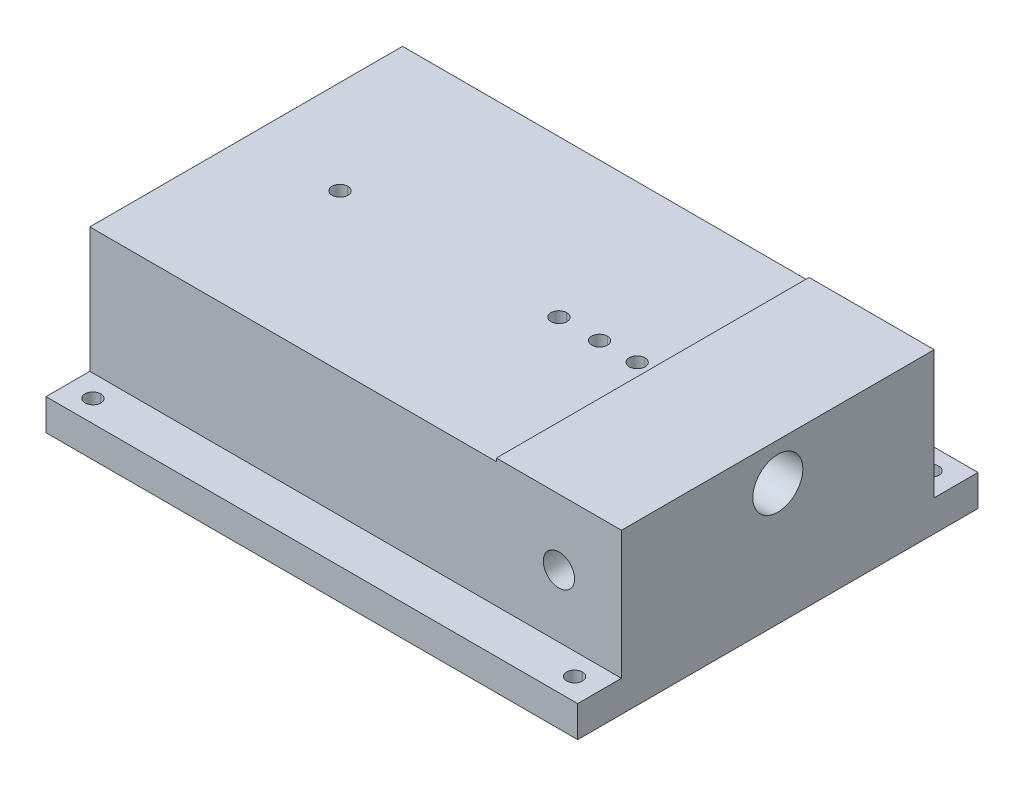
SolidWorks part; units mm, degrees
ref_plane "Front Plane" through (0, 0, 0) normal (0, 0, 1) x (1, 0, 0)
ref_plane "Top Plane" through (0, 0, 0) normal (0, 1, 0) x (1, 0, 0)
ref_plane "Right Plane" through (0, 0, 0) normal (1, 0, 0) x (0, 0, -1)
sketch "Sketch1" plane through (0, 0, 0) normal (0, 1, 0) x (1, 0, 0)
  line L1 (-42.5, 32) -> (42.5, 32)
  line L2 (-42.5, 32) -> (-42.5, -32)
  line L3 (-42.5, -32) -> (42.5, -32)
  line L4 (42.5, 32) -> (42.5, -32)
  point P4 (0, 32)
  point P5 (-42.5, 0)
  dimension "D1" = 85
  dimension "D2" = 64
extrude "Boss-Extrude1" add sketch "Sketch1" along normal blind 25.5
sketch "Sketch2" plane through (0, 25.5, 0) normal (0, 1, 0) x (1, 0, 0)
  line L0 (42.5, -32) -> (42.5, 32) construction
  line L1 (-42.5, 32) -> (42.5, 32)
  line L2 (-42.5, 32) -> (-42.5, 25)
  line L3 (-42.5, 25) -> (42.5, 25)
  line L4 (42.5, 32) -> (42.5, 25)
  line L5 (0, 25) -> (0, -25) construction
  line L6 (-42.5, -32) -> (42.5, -32)
  line L7 (-42.5, -32) -> (-42.5, -25)
  line L8 (-42.5, -25) -> (42.5, -25)
  line L9 (42.5, -32) -> (42.5, -25)
  point P14 (0, 0)
  dimension "D1" = 50
extrude "Cut-Extrude1" cut sketch "Sketch2" against normal offset from surface (20.5 mm away) 5 up to face at (0, 0, 0)
sketch "Sketch3" plane through (0, 25.5, 0) normal (0, 1, 0) x (1, 0, 0)
  line L0 (42.5, -25) -> (-42.5, -25) construction
  line L1 (-42.5, 25) -> (22.5, 25)
  line L2 (-42.5, 25) -> (-42.5, -25)
  line L3 (-42.5, -25) -> (22.5, -25)
  line L4 (22.5, 25) -> (22.5, -25)
  line L5 (42.5, -25) -> (42.5, 25) construction
  dimension "D1" = 20
extrude "Cut-Extrude2" cut sketch "Sketch3" against normal blind 0.5
sketch "Sketch4" plane through (0, 0, 25) normal (0, 0, 1) x (1, 0, 0)
  line L0 (42.5, 5) -> (42.5, 25.5) construction
  line L1 (-42.5, 5) -> (42.5, 5) construction
  circle A0 centre (32.5, 15) radius 2.5
  dimension "D1" = 10
  dimension "D2" = 10
  dimension "D3" = 5
extrude "Cut-Extrude3" cut sketch "Sketch4" against normal blind 5
sketch "Sketch5" plane through (42.5, 0, 0) normal (1, 0, 0) x (0, 0, -1)
  line L0 (-25, 25.5) -> (25, 25.5) construction
  circle A0 centre (0, 19.5) radius 4
  dimension "D1" = 6
  dimension "D2" = 8
extrude "Cut-Extrude4" cut sketch "Sketch5" against normal blind 8
sketch "Sketch6" plane through (34.5, 0, 0) normal (1, 0, 0) x (0, 0, -1)
  circle A0 centre (0, 19.5) radius 1.5
  dimension "D1" = 3
extrude "Cut-Extrude5" cut sketch "Sketch6" against normal offset from surface (64 mm away) 13 up to face at (-42.5, 8.75, 0)
sketch "Sketch7" plane through (0, 25, 0) normal (0, 1, 0) x (1, 0, 0)
  point P13 (-27.5, 0)
  point P14 (7.5, 0)
  point P15 (14, 0)
  point P16 (20, 0)
hole_wizard "Tap Drill Slot for M3x0.5 Tap2" positions "Sketch10" profile "Sketch11" size "M3x0.5" standard "ANSI Metric" slot yes end condition through all
sketch "Sketch10" plane through (0, 5, 0) normal (0, 1, 0) x (1, 0, 0)
  line L0 (-42.5, 25) -> (-42.5, 32) construction
  line L1 (-42.5, 32) -> (42.5, 32) construction
  line L3 (42.5, 32) -> (42.5, 25) construction
  line L4 (42.5, -25) -> (42.5, -32) construction
  line L5 (42.5, -32) -> (-42.5, -32) construction
  line L6 (-42.5, -32) -> (-42.5, -25) construction
  line L8 (-39.77, 28.5) -> (-37.23, 28.5) construction
  point P0 (-38.5, 28.5)
  point P2 (38.5, 28.5)
  point P4 (38.5, -28.5)
  point P6 (-38.5, -28.5)
  dimension "D1" = 4
  dimension "D2" = 3.5
  dimension "D3" = 4
  dimension "D4" = 3.5
  dimension "D5" = 4
  dimension "D6" = 3.5
  dimension "D7" = 4
  dimension "D8" = 3.5
sketch "Sketch11" plane through (-38.5, 5, -28.5) normal (1, 0, 0) x (0, 0, 1)
  line L0 (0, 0) -> (0, 5)
  line L1 (0, 5) -> (1.25, 5)
  line L2 (1.25, 5) -> (1.25, 0)
  line L5 (1.25, 0) -> (0, 0)
  line L11 (0, -6.35) -> (0, 107.95) construction
  dimension "Thru Hole Dia." = 2.5
  dimension "Thru Hole Depth" = 5
hole_wizard "Tap Drill Slot for M3x0.5 Tap1" positions "Sketch12" profile "Sketch13" size "M3x0.5" standard "ANSI Metric" slot yes
sketch "Sketch12" plane through (0, 25, 0) normal (0, 1, 0) x (1, 0, 0)
  line L1 (-28.77, 0) -> (-26.23, 0) construction
  point P0 (-27.5, 0)
  point P5 (7.5, 0)
  point P8 (14, 0)
  point P11 (20, 0)
sketch "Sketch13" plane through (-27.5, 25, 0) normal (1, 0, 0) x (0, 0, 1)
  line L0 (0, 0) -> (0, 6.2501)
  line L1 (0, 6.2501) -> (1.25, 5.499)
  line L2 (1.25, 5.499) -> (1.25, 0)
  line L5 (1.25, 0) -> (0, 0)
  line L10 (0, 6.2501) -> (-1.25, 5.499) construction
  line L11 (0, -6.35) -> (0, 107.95) construction
  dimension "Hole Dia." = 2.5
  dimension "Hole Depth" = 5.499
  dimension "Drill Angle" = 118
